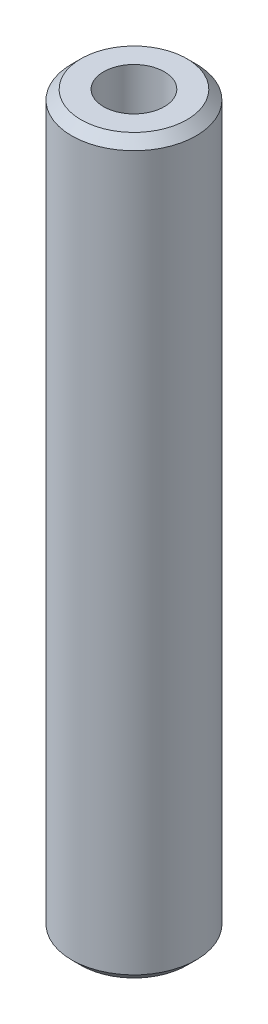
SolidWorks part; units mm, degrees
ref_plane "Front Plane" through (0, 0, 0) normal (0, 0, 1) x (1, 0, 0)
ref_plane "Top Plane" through (0, 0, 0) normal (0, 1, 0) x (1, 0, 0)
ref_plane "Right Plane" through (0, 0, 0) normal (1, 0, 0) x (0, 0, -1)
sketch "Sketch1" plane through (0, 0, 0) normal (0, 1, 0) x (1, 0, 0)
  circle A0 centre (0, 0) radius 25
  dimension "SHAFT_OD" = 50
extrude "Boss-Extrude1" add sketch "Sketch1" along normal blind 294.2339
sketch "Sketch2" plane through (0, 0, 0) normal (0, 1, 0) x (1, 0, 0)
  circle A0 centre (0, 0) radius 12.186
  dimension "BORE_D" = 24.372
extrude "Cut-Extrude1" cut sketch "Sketch2" along normal through all
chamfer "Chamfer1" distance 3.732 angle 45 2 edges at (0, 294.2339, 25) (0, 0, 25)
